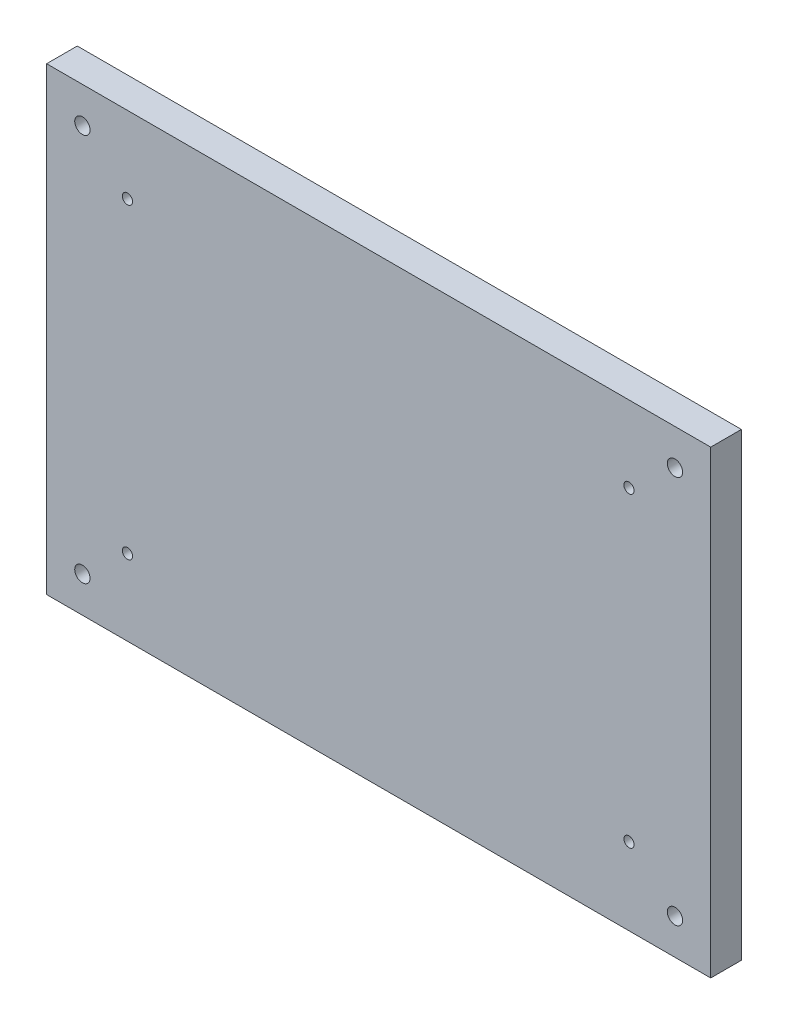
SolidWorks part; units mm, degrees
ref_plane "Płaszczyzna przednia" through (0, 0, 0) normal (0, 0, 1) x (1, 0, 0)
ref_plane "Płaszczyzna górna" through (0, 0, 0) normal (0, 1, 0) x (1, 0, 0)
ref_plane "Płaszczyzna prawa" through (0, 0, 0) normal (1, 0, 0) x (0, 0, -1)
sketch "Sketch1" plane through (0, 0, 0) normal (0, 0, 1) x (1, 0, 0)
  line L1 (0, 0) -> (130, 0)
  line L2 (0, 0) -> (0, 90)
  line L3 (0, 90) -> (130, 90)
  line L4 (130, 0) -> (130, 90)
  line L5 (0, 0) -> (130, 90) construction
  line L6 (0, 90) -> (130, 0) construction
  point P4 (65, 45)
  dimension "D1" = 90
  dimension "D2" = 130
extrude "Boss-Extrude1" add sketch "Sketch1" along normal blind 6
hole_wizard "Ø3.0mm Dowel Hole1" positions "Sketch2" profile "Sketch3" hole size "Ø3.0" standard "ANSI Metric" end condition up to next
sketch "Sketch2" plane through (0, 0, 6) normal (0, 0, 1) x (1, 0, 0)
  point P0 (123, 83)
  point P3 (123, 7)
  point P6 (7, 7)
  point P9 (7, 83)
sketch "Sketch3" plane through (123, 83, 6) normal (1, 0, 0) x (0, -1, 0)
  line L0 (0, 0) -> (0, 6)
  line L1 (0, 6) -> (1.5, 6)
  line L2 (1.5, 6) -> (1.5, 0)
  line L5 (1.5, 0) -> (0, 0)
  line L11 (0, -6.35) -> (0, 107.95) construction
  dimension "Thru Hole Dia." = 3
  dimension "Thru Hole Depth" = 6
hole_wizard "Ø2.0mm Dowel Hole1" positions "Sketch4" profile "Sketch5" hole size "Ø2.0" standard "ANSI Metric" end condition up to next
sketch "Sketch4" plane through (0, 0, 0) normal (0, 0, -1) x (-1, 0, 0)
  point P0 (-114, 75.1)
  point P3 (-114, 15.1)
  point P6 (-15.82, 14.89)
  point P9 (-15.82, 75)
sketch "Sketch5" plane through (114, 75.1, 0) normal (1, 0, 0) x (0, 1, 0)
  line L0 (0, 0) -> (0, 6)
  line L1 (0, 6) -> (1, 6)
  line L2 (1, 6) -> (1, 0)
  line L5 (1, 0) -> (0, 0)
  line L11 (0, -6.35) -> (0, 107.95) construction
  dimension "Thru Hole Dia." = 2
  dimension "Thru Hole Depth" = 6
